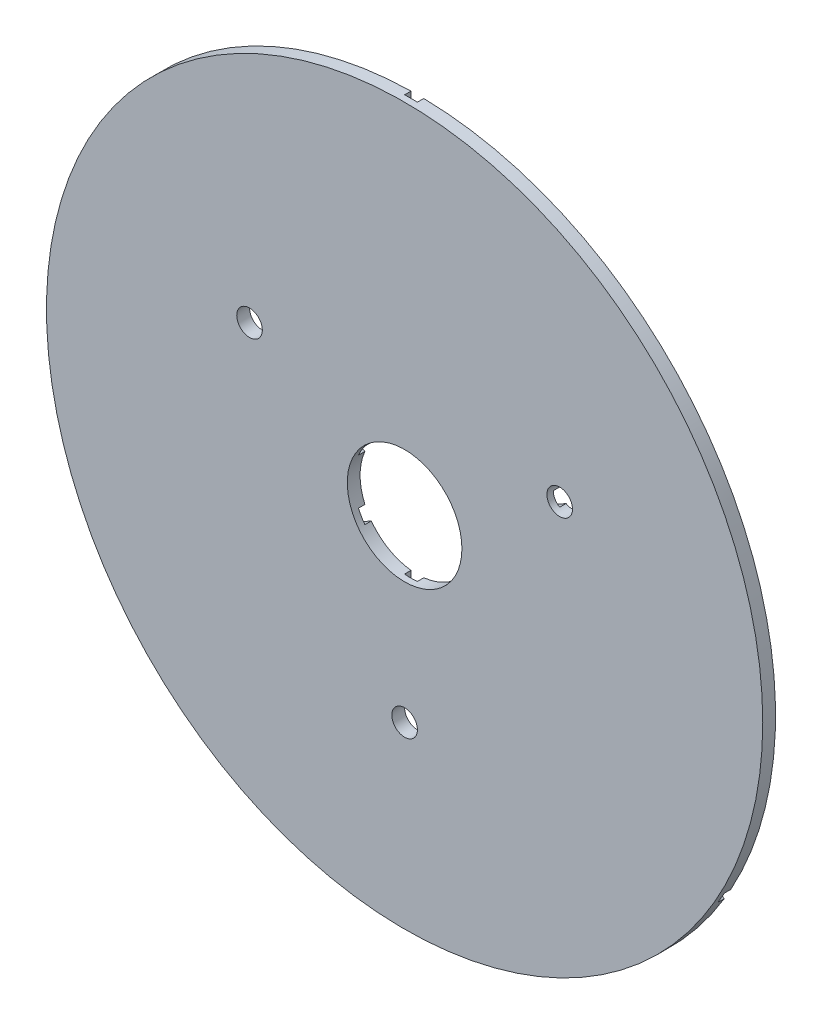
SolidWorks part; units mm, degrees
ref_plane "Front Plane" through (0, 0, 0) normal (0, 0, 1) x (1, 0, 0)
ref_plane "Top Plane" through (0, 0, 0) normal (0, 1, 0) x (1, 0, 0)
ref_plane "Right Plane" through (0, 0, 0) normal (1, 0, 0) x (0, 0, -1)
sketch "Sketch1" plane through (0, 0, 0) normal (0, 0, 1) x (1, 0, 0)
  circle A0 centre (0, 0) radius 88.9
  dimension "D1" = 177.8
extrude "Boss-Extrude1" add sketch "Sketch1" along normal blind 3.175
sketch "Sketch2" plane through (0, 0, 0) normal (0, 0, -1) x (-1, 0, 0)
  line L0 (0, -88.9) -> (0, 88.9) construction
  line L1 (-88.9, 0) -> (88.9, 0) construction
  line L2 (0, 88.9) -> (-76.9897, -44.45) construction
  line L3 (-76.9897, -44.45) -> (76.9897, -44.45) construction
  line L4 (76.9897, -44.45) -> (0, 88.9) construction
  line L5 (-76.9897, -44.45) -> (76.9897, 44.45) construction
  line L6 (76.9897, -44.45) -> (-76.9897, 44.45) construction
  line L7 (-76.1959, -45.8248) -> (77.7834, 43.0752)
  line L8 (77.7834, -43.0752) -> (-76.1959, 45.8248)
  line L9 (1.5875, -88.9) -> (1.5875, 88.9)
  line L10 (-77.7834, -43.0752) -> (76.1959, 45.8248)
  line L11 (76.1959, -45.8248) -> (-77.7834, 43.0752)
  line L12 (-1.5875, -88.9) -> (-1.5875, 88.9)
  circle A0 centre (0, 0) radius 88.9 construction
  circle A2 centre (0, 0) radius 88.9
  circle A3 centre (0, 0) radius 88.9
  circle A4 centre (-38.4948, 22.225) radius 3.175
  circle A5 centre (38.4948, 22.225) radius 3.175
  circle A6 centre (0, -44.45) radius 3.175
  point P6 (0, 0)
  point P11 (0, 0)
  circle M9 centre (0, 0) radius 88.9
  dimension "D5" = 6.35
  dimension "D1" = 30
  dimension "D2" = 1.5875
  dimension "D3" = 1.5875
  dimension "D4" = 0
extrude "Cut-Extrude3" cut sketch "Sketch2" against normal blind 1.5875 contours L7 L12 L11 L10 M9 | L12 L7 L11 | L12 L11 L7 L9 L8 L10 | L11 L9 L7 | L11 L12 L10 | L12 L10 L8 | L10 L8 L9 | L9 L7 L8 | L10 L9 L8 L7 M9 | L11 L8 L7 L9 M9 | L12 L8 L10 L9 M9 | L10 L12 L8 L11 M9 | L12 L9 L11 L7 M9 region at (39.4846, -22.7965, 0) region at (1.0583, -1.8331, 0) region at (0, -21.8514, 0) region at (0, 0, 0) region at (-1.0583, -1.8331, 0) region at (2.1167, 0, 0) region at (18.9238, 10.9257, 0) region at (-2.1167, 0, 0) region at (-39.4846, -22.7965, 0) region at (1.0583, 1.8331, 0) region at (-18.9238, 10.9257, 0) region at (-1.0583, 1.8331, 0) region at (0, 45.5929, 0)
sketch "Sketch3" plane through (0, 0, 3.175) normal (0, 0, 1) x (1, 0, 0)
  circle A0 centre (0, 0) radius 14.224
  dimension "D1" = 28.448
extrude "Cut-Extrude4" cut sketch "Sketch3" against normal through all
extrude "Cut-Extrude5" cut sketch "Sketch2<4>" against normal through all contours L8 A4 L11 | L11 A4 | L8 A4 | L7 A5 L10 | L10 A5 | L7 A5 | L12 A6 | L9 A6 L12 | L9 A6 region at (0, -44.45, 0) region at (2.2384, -44.45, 0) region at (-2.2384, -44.45, 0) region at (39.614, 20.2865, 0) region at (38.4948, 22.225, 0) region at (37.3756, 24.1635, 0) region at (-38.4948, 22.225, 0) region at (-39.614, 20.2865, 0) region at (-37.3756, 24.1635, 0)
sketch "Sketch2<4>" plane through (0, 0, 0) normal (0, 0, -1) x (-1, 0, 0) same geometry as "Sketch2"
